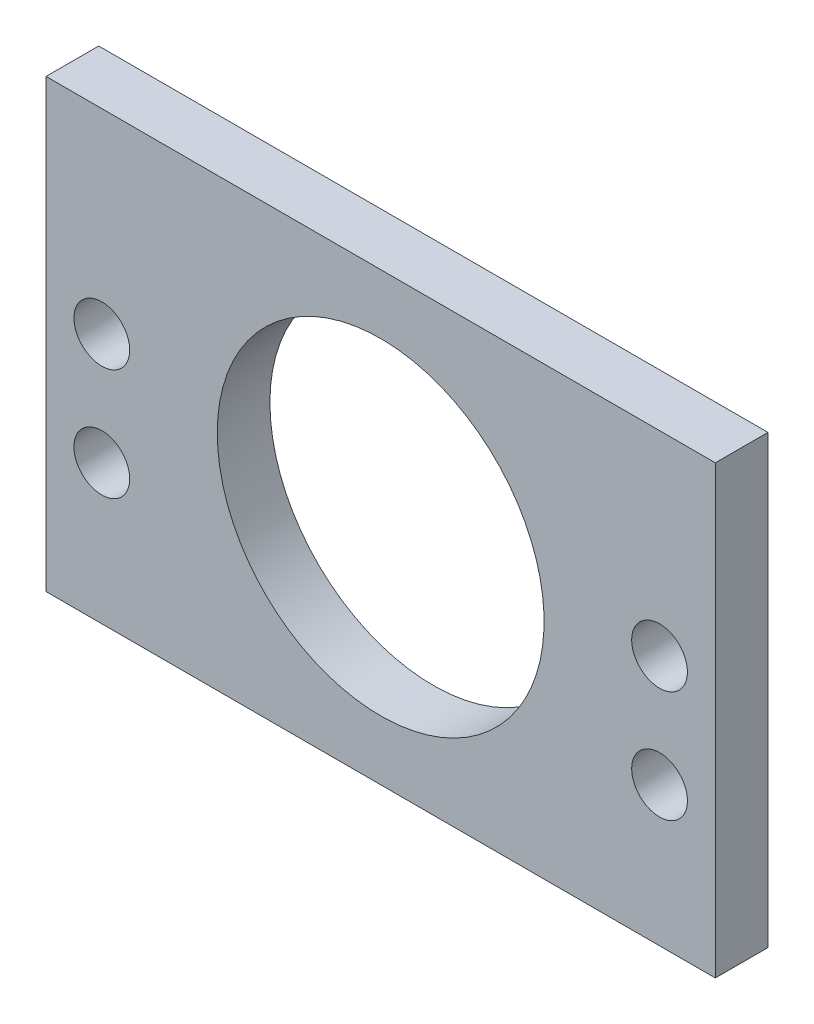
SolidWorks part; units mm, degrees
ref_plane "Front Plane" through (0, 0, 0) normal (0, 0, 1) x (1, 0, 0)
ref_plane "Top Plane" through (0, 0, 0) normal (0, 1, 0) x (1, 0, 0)
ref_plane "Right Plane" through (0, 0, 0) normal (1, 0, 0) x (0, 0, -1)
sketch "Sketch1" plane through (0, 0, 0) normal (0, 0, 1) x (1, 0, 0)
  line L0 (38.1, 50.8) -> (38.1, 25.4) construction
  line L1 (0, 0) -> (76.2, 0)
  line L2 (0, 0) -> (0, 50.8)
  line L3 (0, 50.8) -> (76.2, 50.8)
  line L4 (76.2, 0) -> (76.2, 50.8)
  circle A0 centre (38.1, 25.4) radius 18.6055
  circle A1 centre (6.35, 28.575) radius 3.175
  circle A2 centre (6.35, 15.875) radius 3.175
  circle A3 centre (69.85, 28.575) radius 3.175
  circle A4 centre (69.85, 15.875) radius 3.175
  point P18 (7.2219, 20.5768)
  dimension "D3" = 37.211
  dimension "D5" = 15.875
  dimension "D7" = 6.35
  dimension "D8" = 6.35
  dimension "D9" = 6.35
  dimension "D1" = 76.2
  dimension "D2" = 50.8
  dimension "D4" = 25.4
  dimension "D6" = 12.7
extrude "Boss-Extrude1" add sketch "Sketch1" along normal blind 5.9944
